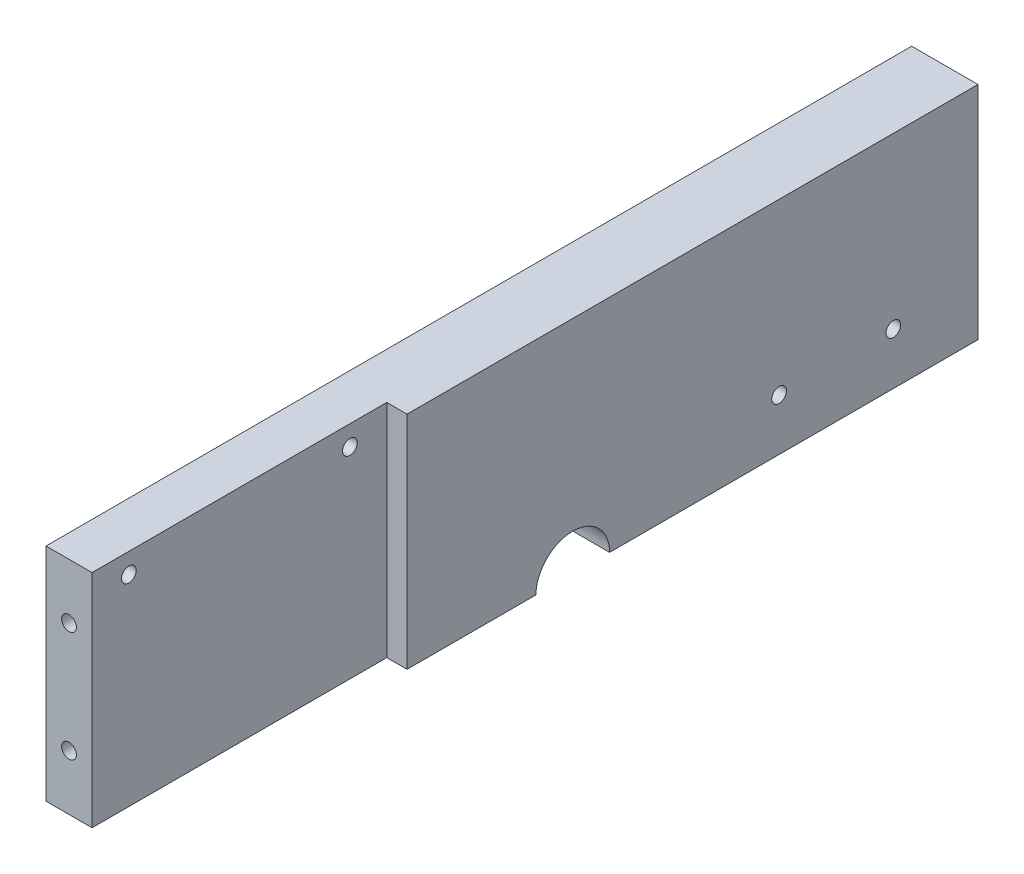
SolidWorks part; units mm, degrees
material "Pin"
ref_plane "Plan de face" through (0, 0, 0) normal (0, 0, 1) x (1, 0, 0)
ref_plane "Plan de dessus" through (0, 0, 0) normal (0, 1, 0) x (1, 0, 0)
ref_plane "Plan de droite" through (0, 0, 0) normal (1, 0, 0) x (0, 0, -1)
sketch "Esquisse1" plane through (0, 0, 0) normal (1, 0, 0) x (0, 0, -1)
  line L0 (-54.8268, 5.1547) -> (-54.8268, -49.3953) construction
  line L1 (-64.8268, 10.6047) -> (170.1732, 10.6047)
  line L2 (-64.8268, 10.6047) -> (-64.8268, -49.3953)
  line L3 (-64.8268, -49.3953) -> (170.1732, -49.3953)
  line L4 (170.1732, 10.6047) -> (170.1732, -49.3953)
  line L5 (5.1732, 5.1547) -> (5.1732, -49.3953) construction
  line L6 (147.1732, -35.3953) -> (161.1732, -35.3953) construction
  line L7 (147.1732, -35.3953) -> (116.1732, -35.3953) construction
  line L8 (116.1732, -35.3953) -> (102.1732, -35.3953) construction
  line L9 (-54.8268, 5.1547) -> (-54.8268, 10.6047) construction
  line L10 (-64.8268, 5.1547) -> (-54.8268, 5.1547) construction
  line L11 (-54.8268, 5.1547) -> (5.1732, 5.1547) construction
  line L12 (5.1732, 5.1547) -> (170.1732, 5.1547) construction
  line L13 (5.1732, 10.6047) -> (5.1732, 5.1547) construction
  line L14 (147.1732, -35.3953) -> (147.1732, -49.3953) construction
  line L15 (15.1732, 10.6047) -> (15.1732, -49.3953)
  line L16 (161.1732, -35.3953) -> (170.1732, -35.3953) construction
  line L19 (102.1732, 2.6047) -> (102.1732, -35.3953) construction
  circle A0 centre (-54.8268, 5.1547) radius 2
  circle A1 centre (5.1732, 5.1547) radius 2
  circle A2 centre (147.1732, -35.3953) radius 2
  circle A3 centre (116.1732, -35.3953) radius 2
  arc A4 (70.1732, -49.3953) -> (50.1732, -49.3953) centre (60.1732, -49.3953) ccw
  dimension "D4" = 4
  dimension "D9" = 4
  dimension "D12" = 10
  dimension "D1" = 60
  dimension "D2" = 235
  dimension "D3" = 54.55
  dimension "D5" = 60
  dimension "D6" = 10
  dimension "D7" = 9
  dimension "D8" = 14
  dimension "D10" = 80
  dimension "D11" = 68
  dimension "D13" = 45
extrude "Boss.-Extru.2" add sketch "Esquisse1" along normal blind 12.5 contours L15 L1 L2 L3 A1 A0 region at (0, -19.5245, 24.8268)
extrude "Boss.-Extru.3" add sketch "Esquisse1<3>" along normal blind 18 contours L1 L15 L3 L4 A3 A2 region at (0, -18.9075, -93.1256)
sketch "Esquisse1<3>" plane through (0, 0, 0) normal (1, 0, 0) x (0, 0, -1) same geometry as "Esquisse1"
ref_plane "Plan1" through (18, -49.3953, -15.1732) normal (0, -1, 0) x (-1, 0, 0)
sketch "Esquisse5" plane through (0, 0, 64.8268) normal (0, 0, 1) x (1, 0, 0)
  line L0 (6.25, 10.6047) -> (6.25, -4.3953) construction
  line L1 (12.5, 10.6047) -> (0, 10.6047) construction
  line L2 (6.25, -4.3953) -> (6.25, -34.3953) construction
  line L3 (6.25, -34.3953) -> (6.25, -49.3953) construction
  line L4 (12.5, -49.3953) -> (0, -49.3953) construction
  circle A0 centre (6.25, -4.3953) radius 2
  circle A1 centre (6.25, -34.3953) radius 2
  dimension "D1" = 4
  dimension "D2" = 15
extrude "Enlèv. mat.-Extru.2" cut sketch "Esquisse5" against normal blind 10
sketch "Esquisse6" plane through (0, -49.3953, 0) normal (0, -1, 0) x (1, 0, 0)
  line L0 (9, -170.1732) -> (9, -155.1732) construction
  line L1 (18, -170.1732) -> (0, -170.1732) construction
  line L2 (9, -155.1732) -> (9, -85.1732) construction
  line L3 (9, -85.1732) -> (9, -70.1732) construction
  line L4 (18, -70.1732) -> (0, -70.1732) construction
  dimension "D1" = 15
sketch "Esquisse7" plane through (0, -49.3953, 0) normal (0, -1, 0) x (1, 0, 0)
  line L0 (6.25, 64.8268) -> (6.25, 49.8268) construction
  line L1 (12.5, 64.8268) -> (0, 64.8268) construction
  line L2 (6.25, 49.8268) -> (6.25, -0.1732) construction
  line L3 (9, -50.1732) -> (9, -32.6732) construction
  line L4 (18, -50.1732) -> (0, -50.1732) construction
  line L5 (12.5, -15.1732) -> (9, -15.1732) construction
  line L6 (9, -15.1732) -> (9, -32.6732) construction
  line L7 (9, -15.1732) -> (6.25, -15.1732) construction
  line L8 (6.25, -15.1732) -> (6.25, -0.1732) construction
  dimension "D1" = 15
